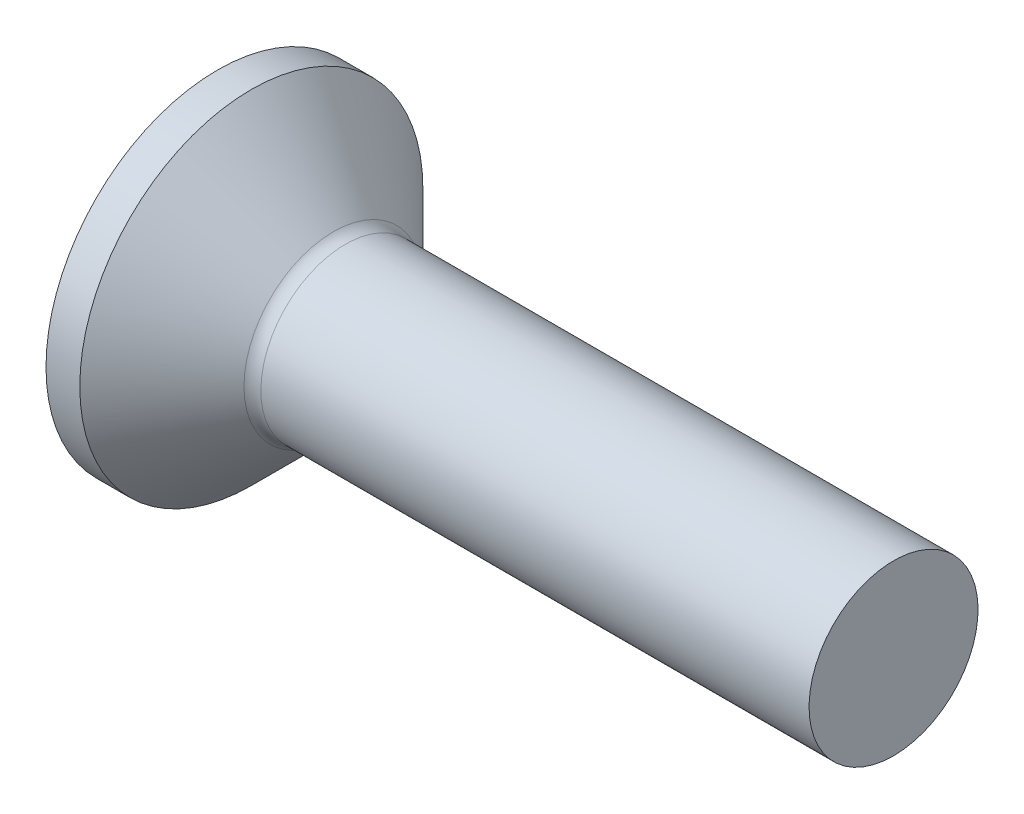
SolidWorks part; units mm, degrees
ref_plane "Front" through (0, 0, 0) normal (0, 0, 1) x (1, 0, 0)
ref_plane "Top" through (0, 0, 0) normal (0, 1, 0) x (1, 0, 0)
ref_plane "Right" through (0, 0, 0) normal (1, 0, 0) x (0, 0, -1)
sketch "Sketch1" plane through (-0.4925, -1.5075, 0) normal (0, 0, 1) x (0, 1, 0)
  line L0 (1.5075, -0.4925) -> (2.5225, -0.4925)
  line L1 (2.5225, -0.4925) -> (2.5225, -0.6925)
  line L2 (2.5225, -0.6925) -> (2.0075, -1.2075)
  line L3 (2.0075, -1.2075) -> (2.0075, -4.4925)
  line L4 (2.0075, -4.4925) -> (1.5075, -4.4925)
  line L5 (1.5075, -4.4925) -> (1.5075, -0.4925)
  line L6 (1.5075, 2.03) -> (1.5075, -4.03) construction
  dimension "b" = 0.2
  dimension "dk" = 2.03
  dimension "l" = 4
  dimension "d" = 1
  dimension "Angle" = 45
revolve "Base-Revolve" add sketch "Sketch1" angle 360 about L6
fillet "Fillet1" radius 0.1 1 edges at (0.715, -0.5, 0)
